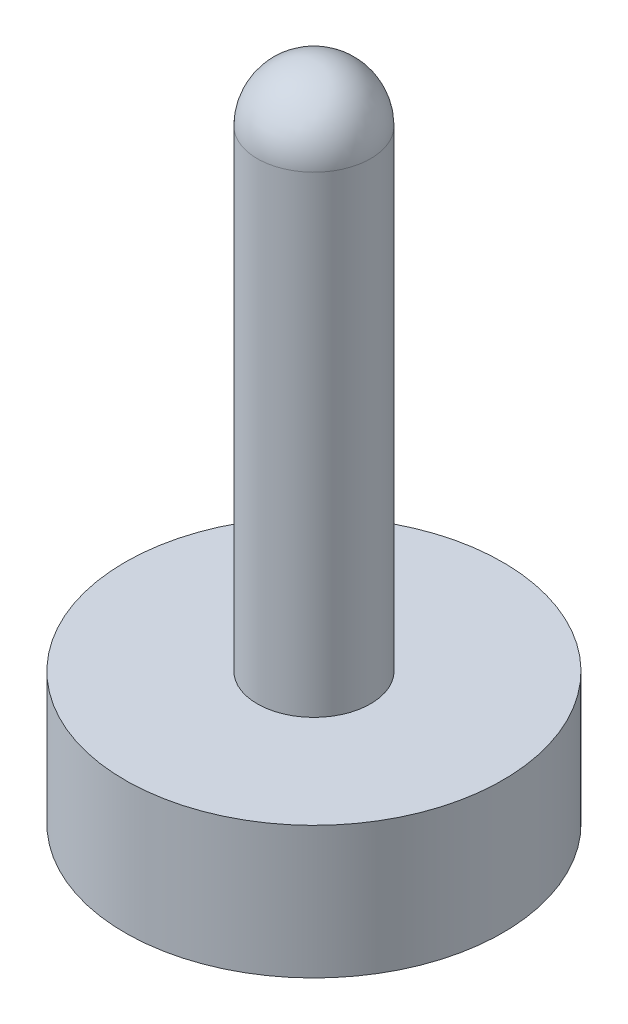
SolidWorks part; units mm, degrees
ref_plane "Front Plane" through (0, 0, 0) normal (0, 0, 1) x (1, 0, 0)
ref_plane "Top Plane" through (0, 0, 0) normal (0, 1, 0) x (1, 0, 0)
ref_plane "Right Plane" through (0, 0, 0) normal (1, 0, 0) x (0, 0, -1)
sketch "Sketch1" plane through (0, 0, 0) normal (0, 0, 1) x (1, 0, 0)
  line L0 (0, 0) -> (2, 0)
  line L1 (2, 0) -> (2, 1.4)
  line L2 (2, 1.4) -> (0.6, 1.4)
  line L3 (0.6, 1.4) -> (0.6, 6.4)
  line L4 (0.6, 6.4) -> (0, 6.4)
  line L5 (0, 6.4) -> (0, 0)
  dimension "D1" = 2
  dimension "D2" = 1.4
  dimension "D3" = 0.6
  dimension "D4" = 5
revolve "Revolve1" add sketch "Sketch1" angle 360 about L5
dome "Dome1" faces to dome 1 distance 0.6 reverse direction no elliptical dome no face at (-0.6, 6.4, 0) parameters "D1"=0.6
